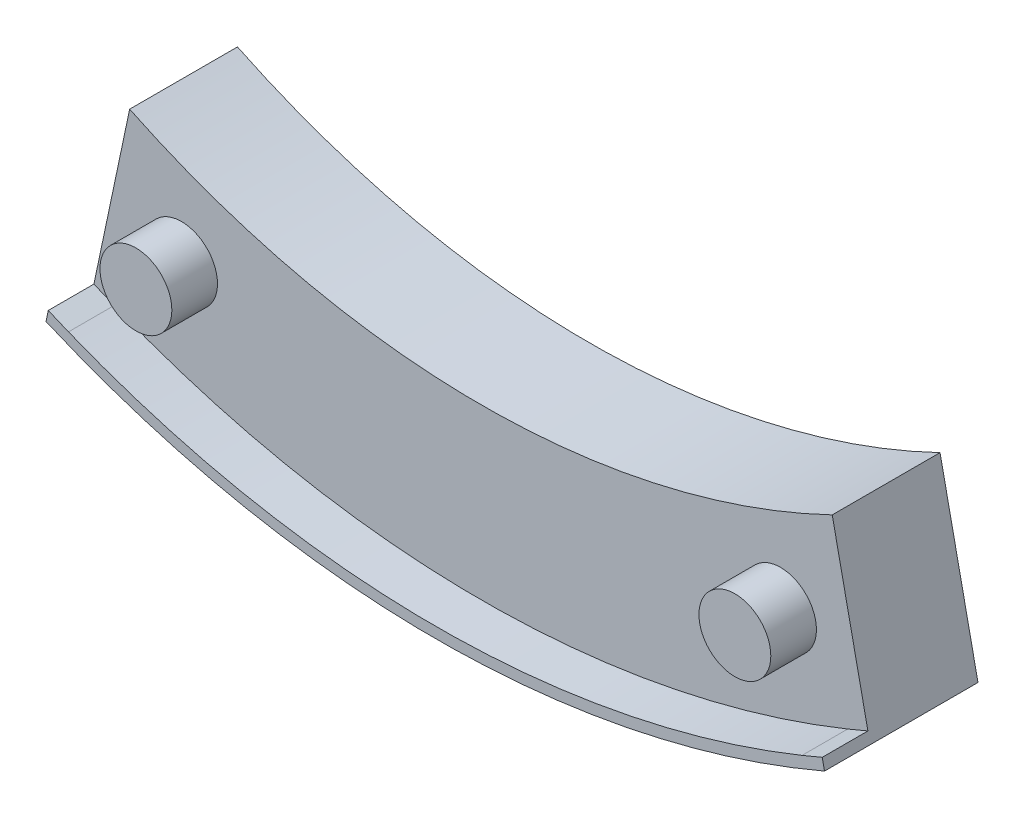
SolidWorks part; units mm, degrees
ref_plane "Front Plane" through (0, 0, 0) normal (0, 0, 1) x (1, 0, 0)
ref_plane "Top Plane" through (0, 0, 0) normal (0, 1, 0) x (1, 0, 0)
ref_plane "Right Plane" through (0, 0, 0) normal (1, 0, 0) x (0, 0, -1)
sketch "Sketch1" plane through (0, 0, 0) normal (0, 0, 1) x (1, 0, 0)
  line L0 (-11, 0) -> (-21.6692, -50.5514)
  line L5 (11, 0) -> (21.6565, -50.5569)
  line L6 (21.5296, -49.955) -> (20.4046, -50.4252)
  line L7 (-21.5432, -49.9549) -> (-20.4182, -50.425)
  line L11 (11, 0) -> (-11, 0)
  circle A2 centre (16.666, -46.502) radius 2
  circle A3 centre (-16.666, -46.502) radius 2
  circle A4 centre (0, 0) radius 66.0177
  arc A5 (-21.6692, -50.5514) -> (21.6565, -50.5569) centre (0, 0) ccw
  circle A6 centre (0, 0) radius 45
  arc A7 (-0.0066, -54.3997) -> (20.4046, -50.4252) centre (-0.0067, -0.0014) ccw
  arc A8 (-0.0066, -54.3997) -> (-20.4182, -50.425) centre (-0.0067, -0.0014) cw
  point P8 (0, 0)
  point P11 (0, 0)
  dimension "D2" = 55
  dimension "D4" = 132.0353
  dimension "D1" = 23.82
  dimension "D3" = 22
extrude "Boss-Extrude1" add sketch "Sketch1" along normal blind 6 contours L0 A5 L5 L11 A3 A2 region at (-0.0087, -48.3985, 0)
extrude "Boss-Extrude2" add sketch "Sketch1<3>" along normal blind 8.54 contours A3 | A2 | A7 A8 L7 L0 A5 L5 L6 region at (-21.1489, -50.5924, 0) region at (16.666, -46.502, 0) region at (-16.666, -46.502, 0)
sketch "Sketch1<3>" plane through (0, 0, 0) normal (0, 0, 1) x (1, 0, 0) same geometry as "Sketch1"
